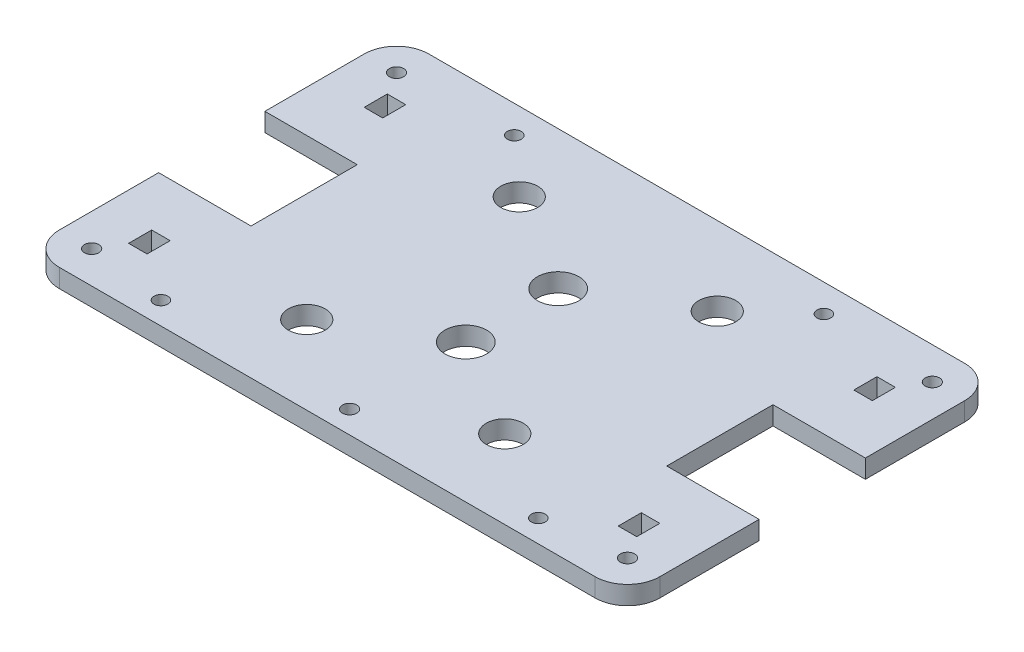
SolidWorks part; units mm, degrees
ref_plane "Front Plane" through (0, 0, 0) normal (0, 0, 1) x (1, 0, 0)
ref_plane "Top Plane" through (0, 0, 0) normal (0, 1, 0) x (1, 0, 0)
ref_plane "Right Plane" through (0, 0, 0) normal (1, 0, 0) x (0, 0, -1)
sketch "Sketch1" plane through (0, 0, 0) normal (0, 1, 0) x (1, 0, 0)
  line L0 (45, -11.5) -> (45, 11.5)
  line L1 (-58, -40) -> (58, -40)
  line L2 (-65, -33) -> (-65, -11.5)
  line L3 (-58, 40) -> (58, 40)
  line L4 (65, -33) -> (65, -11.5)
  line L5 (-65, -40) -> (65, 40) construction
  line L6 (-65, 40) -> (65, -40) construction
  line L8 (45, -11.5) -> (65, -11.5)
  line L9 (65, 11.5) -> (65, 33)
  line L10 (45, 11.5) -> (65, 11.5)
  line L15 (0, 0) -> (0, 29.598) construction
  line L16 (-45, -11.5) -> (-65, -11.5)
  line L18 (-45, 11.5) -> (-65, 11.5)
  line L23 (-65, 11.5) -> (-65, 33)
  line L24 (0, 0) -> (19.3136, 0) construction
  line L25 (55, -23) -> (51, -23)
  line L26 (55, -23) -> (55, -28)
  line L27 (55, -28) -> (51, -28)
  line L28 (51, -23) -> (51, -28)
  line L29 (55, 28) -> (51, 28)
  line L30 (51, 23) -> (51, 28)
  line L31 (55, 23) -> (51, 23)
  line L32 (55, 23) -> (55, 28)
  line L33 (-55, -28) -> (-51, -28)
  line L34 (-51, -23) -> (-51, -28)
  line L35 (-55, -23) -> (-51, -23)
  line L36 (-55, -23) -> (-55, -28)
  line L37 (-55, 23) -> (-55, 28)
  line L38 (-55, 23) -> (-51, 23)
  line L39 (-51, 23) -> (-51, 28)
  line L40 (-55, 28) -> (-51, 28)
  line L89 (-45, 11.5) -> (-45, -11.5)
  line L93 (-65, 40) -> (-65, -40) construction
  line L94 (-65, -40) -> (65, -40) construction
  line L95 (65, -40) -> (65, 40) construction
  line L96 (65, 40) -> (-65, 40) construction
  line L97 (-65, -40) -> (65, 40) construction
  line L98 (-65, 40) -> (65, -40) construction
  circle A0 centre (58, 33) radius 1.55
  circle A1 centre (58, -33) radius 1.55
  circle A2 centre (-58, -33) radius 1.55
  circle A3 centre (-58, 33) radius 1.55
  circle A4 centre (33.5, 34) radius 1.5
  arc A6 (42, 32.5) -> (42, 35.5) centre (42, 34) ccw construction
  arc A7 (25, 35.5) -> (25, 32.5) centre (25, 34) ccw construction
  circle A8 centre (-33.5, 34) radius 1.5
  circle A9 centre (-40.8473, -35.1576) radius 1.5
  arc A10 (-40.8211, -33.6578) -> (-40.8735, -36.6574) centre (-40.8473, -35.1576) ccw construction
  circle A11 centre (0, -35.1562) radius 1.55
  arc A12 (0, -33.6562) -> (0, -36.6562) centre (0, -35.1562) ccw construction
  circle A13 centre (40.8473, -35.1576) radius 1.5
  circle A14 centre (0, -10) radius 4.5
  circle A15 centre (0, 10) radius 4.5
  circle A16 centre (21.4348, -23) radius 4
  circle A17 centre (-21.4348, -23) radius 4
  circle A18 centre (-21.4348, 23) radius 4
  circle A19 centre (21.4348, 23) radius 4
  arc A20 (-58, -40) -> (-65, -33) centre (-58, -33) cw
  arc A21 (58, -40) -> (65, -33) centre (58, -33) ccw
  arc A22 (58, 40) -> (65, 33) centre (58, 33) cw
  arc A23 (-65, 33) -> (-58, 40) centre (-58, 33) cw
  point P0 (0, 0)
  point P42 (-45, -10)
  point P43 (0, 0)
  point P44 (0, 0)
  point P45 (-45, -18.7047)
  point P46 (0, 0)
  point P47 (-45, -6.9712)
  point P48 (-45, -2.1976)
  point P49 (-45, -9.2377)
  point P50 (0, 0)
  point P51 (0, 0)
  point P52 (45, 10.9874)
  point P101 (23.5, 34)
  dimension "D3" = 7
  dimension "D5" = 3.1
  dimension "D6" = 7
  dimension "D7" = 7
  dimension "D10" = 5
  dimension "D11" = 4
  dimension "D21" = 8.5
  dimension "D22" = 3
  dimension "D23" = 9
  dimension "D25" = 8
  dimension "D27" = 43.5652
  dimension "D28" = 7
  dimension "D1" = 80
  dimension "D2" = 130
  dimension "D4" = 7
  dimension "D8" = 20
  dimension "D9" = 23
  dimension "D12" = 5
  dimension "D13" = 3
  dimension "D20" = 28.5
  dimension "D24" = 10
  dimension "D26" = 17
extrude "Boss-Extrude1" add sketch "Sketch1" along normal blind 4
